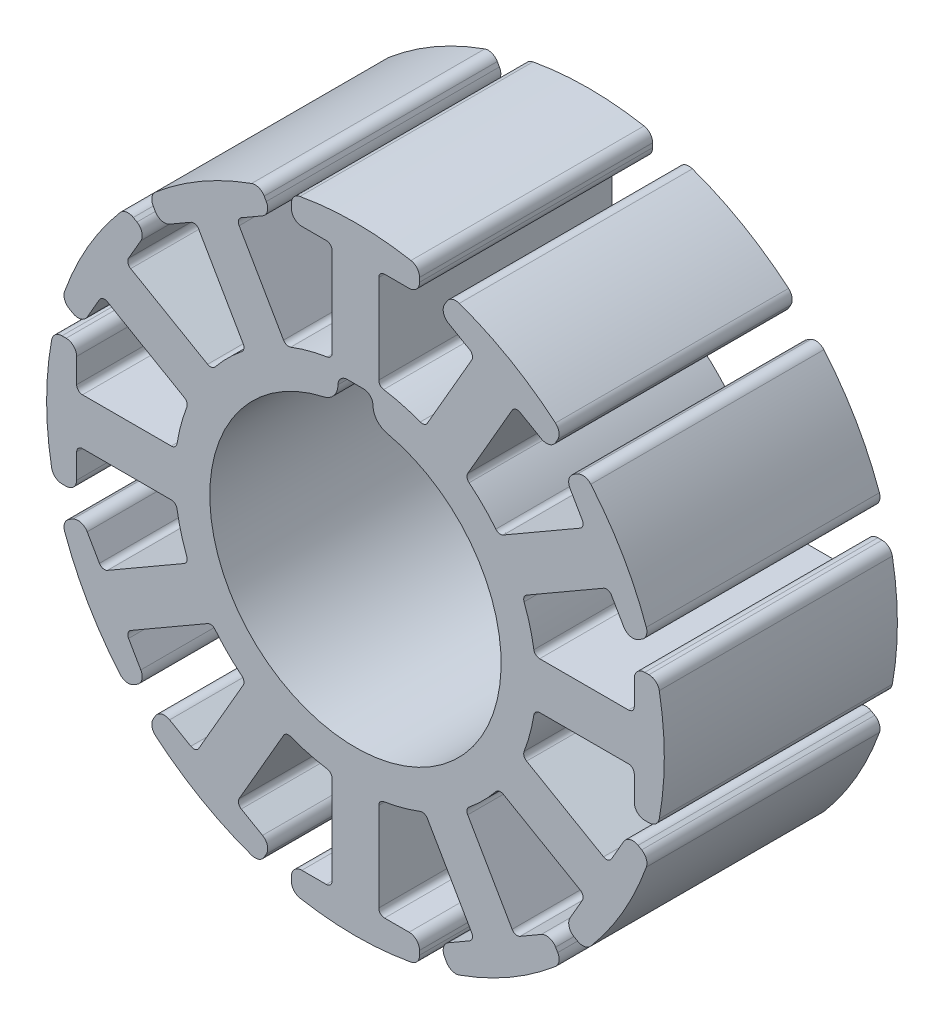
SolidWorks part; units mm, degrees
material "AISI 347 軟ｽﾃﾝﾚｽ鋼 (SS)"
ref_plane "正面" through (0, 0, 0) normal (0, 0, 1) x (1, 0, 0)
ref_plane "平面" through (0, 0, 0) normal (0, 1, 0) x (1, 0, 0)
ref_plane "右側面" through (0, 0, 0) normal (1, 0, 0) x (0, 0, -1)
sketch "ｽｹｯﾁ1" plane through (0, 0, 0) normal (0, 0, 1) x (1, 0, 0)
  line L0 (0, 26.5) -> (0, 0) construction
  line L1 (-5.5, 25.923) -> (5.5, 25.923) construction
  line L2 (-2, 23.923) -> (-2, 15.3704)
  line L3 (2, 23.923) -> (2, 15.3704)
  line L4 (13.6935, 19.7179) -> (9.4173, 12.3112)
  line L5 (16.7246, 17.9679) -> (13.6935, 19.7179)
  line L6 (-5.5, 25.923) -> (-5.5, 23.923)
  line L7 (-5.5, 23.923) -> (-2, 23.923)
  line L8 (5.5, 25.923) -> (5.5, 23.923)
  line L9 (5.5, 23.923) -> (2, 23.923)
  line L10 (17.7246, 19.6999) -> (16.7246, 17.9679)
  line L11 (8.1983, 25.1999) -> (7.1983, 23.4679)
  line L12 (7.1983, 23.4679) -> (10.2294, 21.7179)
  line L13 (10.2294, 21.7179) -> (5.9532, 14.3112)
  line L14 (21.7179, 10.2294) -> (14.3112, 5.9532)
  line L15 (23.4679, 7.1983) -> (21.7179, 10.2294)
  line L16 (25.1999, 8.1983) -> (23.4679, 7.1983)
  line L17 (19.6999, 17.7246) -> (17.9679, 16.7246)
  line L18 (17.9679, 16.7246) -> (19.7179, 13.6935)
  line L19 (19.7179, 13.6935) -> (12.3112, 9.4173)
  line L20 (23.923, -2) -> (15.3704, -2)
  line L21 (23.923, -5.5) -> (23.923, -2)
  line L22 (25.923, -5.5) -> (23.923, -5.5)
  line L23 (25.923, 5.5) -> (23.923, 5.5)
  line L24 (23.923, 5.5) -> (23.923, 2)
  line L25 (23.923, 2) -> (15.3704, 2)
  line L26 (19.7179, -13.6935) -> (12.3112, -9.4173)
  line L27 (17.9679, -16.7246) -> (19.7179, -13.6935)
  line L28 (19.6999, -17.7246) -> (17.9679, -16.7246)
  line L29 (25.1999, -8.1983) -> (23.4679, -7.1983)
  line L30 (23.4679, -7.1983) -> (21.7179, -10.2294)
  line L31 (21.7179, -10.2294) -> (14.3112, -5.9532)
  line L32 (10.2294, -21.7179) -> (5.9532, -14.3112)
  line L33 (7.1983, -23.4679) -> (10.2294, -21.7179)
  line L34 (8.1983, -25.1999) -> (7.1983, -23.4679)
  line L35 (17.7246, -19.6999) -> (16.7246, -17.9679)
  line L36 (16.7246, -17.9679) -> (13.6935, -19.7179)
  line L37 (13.6935, -19.7179) -> (9.4173, -12.3112)
  line L38 (-2, -23.923) -> (-2, -15.3704)
  line L39 (-5.5, -23.923) -> (-2, -23.923)
  line L40 (-5.5, -25.923) -> (-5.5, -23.923)
  line L41 (5.5, -25.923) -> (5.5, -23.923)
  line L42 (5.5, -23.923) -> (2, -23.923)
  line L43 (2, -23.923) -> (2, -15.3704)
  line L44 (-13.6935, -19.7179) -> (-9.4173, -12.3112)
  line L45 (-16.7246, -17.9679) -> (-13.6935, -19.7179)
  line L46 (-17.7246, -19.6999) -> (-16.7246, -17.9679)
  line L47 (-8.1983, -25.1999) -> (-7.1983, -23.4679)
  line L48 (-7.1983, -23.4679) -> (-10.2294, -21.7179)
  line L49 (-10.2294, -21.7179) -> (-5.9532, -14.3112)
  line L50 (-21.7179, -10.2294) -> (-14.3112, -5.9532)
  line L51 (-23.4679, -7.1983) -> (-21.7179, -10.2294)
  line L52 (-25.1999, -8.1983) -> (-23.4679, -7.1983)
  line L53 (-19.6999, -17.7246) -> (-17.9679, -16.7246)
  line L54 (-17.9679, -16.7246) -> (-19.7179, -13.6935)
  line L55 (-19.7179, -13.6935) -> (-12.3112, -9.4173)
  line L56 (-23.923, 2) -> (-15.3704, 2)
  line L57 (-23.923, 5.5) -> (-23.923, 2)
  line L58 (-25.923, 5.5) -> (-23.923, 5.5)
  line L59 (-25.923, -5.5) -> (-23.923, -5.5)
  line L60 (-23.923, -5.5) -> (-23.923, -2)
  line L61 (-23.923, -2) -> (-15.3704, -2)
  line L62 (-19.7179, 13.6935) -> (-12.3112, 9.4173)
  line L63 (-17.9679, 16.7246) -> (-19.7179, 13.6935)
  line L64 (-19.6999, 17.7246) -> (-17.9679, 16.7246)
  line L65 (-25.1999, 8.1983) -> (-23.4679, 7.1983)
  line L66 (-23.4679, 7.1983) -> (-21.7179, 10.2294)
  line L67 (-21.7179, 10.2294) -> (-14.3112, 5.9532)
  line L68 (-10.2294, 21.7179) -> (-5.9532, 14.3112)
  line L69 (-7.1983, 23.4679) -> (-10.2294, 21.7179)
  line L70 (-8.1983, 25.1999) -> (-7.1983, 23.4679)
  line L71 (-17.7246, 19.6999) -> (-16.7246, 17.9679)
  line L72 (-16.7246, 17.9679) -> (-13.6935, 19.7179)
  line L73 (-13.6935, 19.7179) -> (-9.4173, 12.3112)
  circle A0 centre (0, 0) radius 26.5 construction
  arc A1 (-2, 15.3704) -> (-5.9532, 14.3112) centre (0, 0) ccw
  circle A2 centre (0, 0) radius 12.5
  arc A3 (-5.5, 25.923) -> (5.5, 25.923) centre (0, 0) cw
  arc A4 (8.1983, 25.1999) -> (17.7246, 19.6999) centre (0, 0) cw
  arc A5 (19.6999, 17.7246) -> (25.1999, 8.1983) centre (0, 0) cw
  arc A6 (25.923, 5.5) -> (25.923, -5.5) centre (0, 0) cw
  arc A7 (25.1999, -8.1983) -> (19.6999, -17.7246) centre (0, 0) cw
  arc A8 (17.7246, -19.6999) -> (8.1983, -25.1999) centre (0, 0) cw
  arc A9 (5.5, -25.923) -> (-5.5, -25.923) centre (0, 0) cw
  arc A10 (-8.1983, -25.1999) -> (-17.7246, -19.6999) centre (0, 0) cw
  arc A11 (-19.6999, -17.7246) -> (-25.1999, -8.1983) centre (0, 0) cw
  arc A12 (-25.923, -5.5) -> (-25.923, 5.5) centre (0, 0) cw
  arc A13 (-25.1999, 8.1983) -> (-19.6999, 17.7246) centre (0, 0) cw
  arc A14 (-17.7246, 19.6999) -> (-8.1983, 25.1999) centre (0, 0) cw
  arc A15 (5.9532, 14.3112) -> (2, 15.3704) centre (0, 0) ccw
  arc A16 (12.3112, 9.4173) -> (9.4173, 12.3112) centre (0, 0) ccw
  arc A17 (15.3704, 2) -> (14.3112, 5.9532) centre (0, 0) ccw
  arc A18 (14.3112, -5.9532) -> (15.3704, -2) centre (0, 0) ccw
  arc A19 (9.4173, -12.3112) -> (12.3112, -9.4173) centre (0, 0) ccw
  arc A20 (2, -15.3704) -> (5.9532, -14.3112) centre (0, 0) ccw
  arc A21 (-5.9532, -14.3112) -> (-2, -15.3704) centre (0, 0) ccw
  arc A22 (-12.3112, -9.4173) -> (-9.4173, -12.3112) centre (0, 0) ccw
  arc A23 (-15.3704, -2) -> (-14.3112, -5.9532) centre (0, 0) ccw
  arc A24 (-14.3112, 5.9532) -> (-15.3704, 2) centre (0, 0) ccw
  arc A25 (-9.4173, 12.3112) -> (-12.3112, 9.4173) centre (0, 0) ccw
  point P105 (0, 0)
  dimension "D1" = 53
  dimension "D4" = 25
  dimension "D5" = 31
  dimension "D2" = 2
  dimension "D3" = 2
  dimension "D6" = 11
  dimension "D7" = 2
  dimension "D8" = 12
extrude "ﾎﾞｽ - 押し出し1" add sketch "ｽｹｯﾁ1" along normal blind 20
fillet "ﾌｨﾚｯﾄ1" radius 0.9 4 edges at (-16.7246, 17.9679, 10) (-17.7246, 19.6999, 10) (-8.1983, 25.1999, 10) (-7.1983, 23.4679, 10)
fillet "ﾌｨﾚｯﾄ2" radius 0.9 12 edges at (23.4679, 7.1983, 10) (16.7246, 17.9679, 10) (17.9679, 16.7246, 10) (25.1999, 8.1983, 10) (5.5, 23.923, 10) (19.6999, 17.7246, 10) (17.7246, 19.6999, 10) (7.1983, 23.4679, 10) (8.1983, 25.1999, 10) (5.5, 25.923, 10) (-5.5, 23.923, 10) (-5.5, 25.923, 10)
fillet "ﾌｨﾚｯﾄ3" radius 0.9 8 edges at (19.6999, -17.7246, 10) (17.9679, -16.7246, 10) (25.1999, -8.1983, 10) (23.4679, -7.1983, 10) (23.923, 5.5, 10) (23.923, -5.5, 10) (25.923, -5.5, 10) (25.923, 5.5, 10)
fillet "ﾌｨﾚｯﾄ4" radius 0.9 24 edges at (-19.6999, 17.7246, 10) (-17.9679, 16.7246, 10) (-25.1999, 8.1983, 10) (-23.4679, 7.1983, 10) (-23.923, 5.5, 10) (-25.923, 5.5, 10) (-23.923, -5.5, 10) (-25.923, -5.5, 10) (-23.4679, -7.1983, 10) (-25.1999, -8.1983, 10) (-19.6999, -17.7246, 10) (-17.9679, -16.7246, 10) (-16.7246, -17.9679, 10) (-17.7246, -19.6999, 10) (-8.1983, -25.1999, 10) (-7.1983, -23.4679, 10) (-5.5, -23.923, 10) (-5.5, -25.923, 10) (5.5, -23.923, 10) (5.5, -25.923, 10) (8.1983, -25.1999, 10) (7.1983, -23.4679, 10) (17.7246, -19.6999, 10) (16.7246, -17.9679, 10)
fillet "ﾌｨﾚｯﾄ5" radius 0.5 26 edges at (-21.7179, -10.2294, 10) (-14.3112, -5.9532, 10) (-19.7179, -13.6935, 10) (-12.3112, -9.4173, 10) (-13.6935, -19.7179, 10) (-9.4173, -12.3112, 10) (-10.2294, -21.7179, 10) (-5.9532, -14.3112, 10) (-2, -23.923, 10) (-2, -15.3704, 10) (2, -23.923, 10) (2, -15.3704, 10) (5.9532, -14.3112, 10) (10.2294, -21.7179, 10) (13.6935, -19.7179, 10) (9.4173, -12.3112, 10) (19.7179, -13.6935, 10) (12.3112, -9.4173, 10) (21.7179, -10.2294, 10) (14.3112, -5.9532, 10) (15.3704, -2, 10) (23.923, -2, 10) (23.923, 2, 10) (15.3704, 2, 10) (14.3112, 5.9532, 10) (21.7179, 10.2294, 10)
fillet "ﾌｨﾚｯﾄ6" radius 0.5 22 edges at (19.7179, 13.6935, 10) (12.3112, 9.4173, 10) (9.4173, 12.3112, 10) (13.6935, 19.7179, 10) (10.2294, 21.7179, 10) (5.9532, 14.3112, 10) (-2, 15.3704, 10) (-2, 23.923, 10) (2, 23.923, 10) (-10.2294, 21.7179, 10) (-9.4173, 12.3112, 10) (-19.7179, 13.6935, 10) (-13.6935, 19.7179, 10) (-21.7179, 10.2294, 10) (-14.3112, 5.9532, 10) (2, 15.3704, 10) (-5.9532, 14.3112, 10) (-12.3112, 9.4173, 10) (-23.923, 2, 10) (-15.3704, 2, 10) (-23.923, -2, 10) (-15.3704, -2, 10)
sketch "ｽｹｯﾁ3" plane through (0, 0, 20) normal (0, 0, 1) x (1, 0, 0)
  line L1 (-1.5, 10.5) -> (1.5, 10.5)
  line L2 (-1.5, 10.5) -> (-1.5, 14.5)
  line L3 (-1.5, 14.5) -> (1.5, 14.5)
  line L4 (1.5, 10.5) -> (1.5, 14.5)
  line L5 (-1.5, 10.5) -> (1.5, 14.5) construction
  line L6 (-1.5, 14.5) -> (1.5, 10.5) construction
  circle A0 centre (0, 0) radius 12.5 construction
  point P0 (0, 12.5)
  dimension "D1" = 3
  dimension "D2" = 2
extrude "ｶｯﾄ - 押し出し1" cut sketch "ｽｹｯﾁ3" against normal through all
fillet "ﾌｨﾚｯﾄ7" radius 1.55 2 edges at (1.5, 12.4097, 10) (-1.5, 12.4097, 10)
fillet "ﾌｨﾚｯﾄ8" radius 0.8 2 edges at (1.5, 14.5, 10) (-1.5, 14.5, 10)
